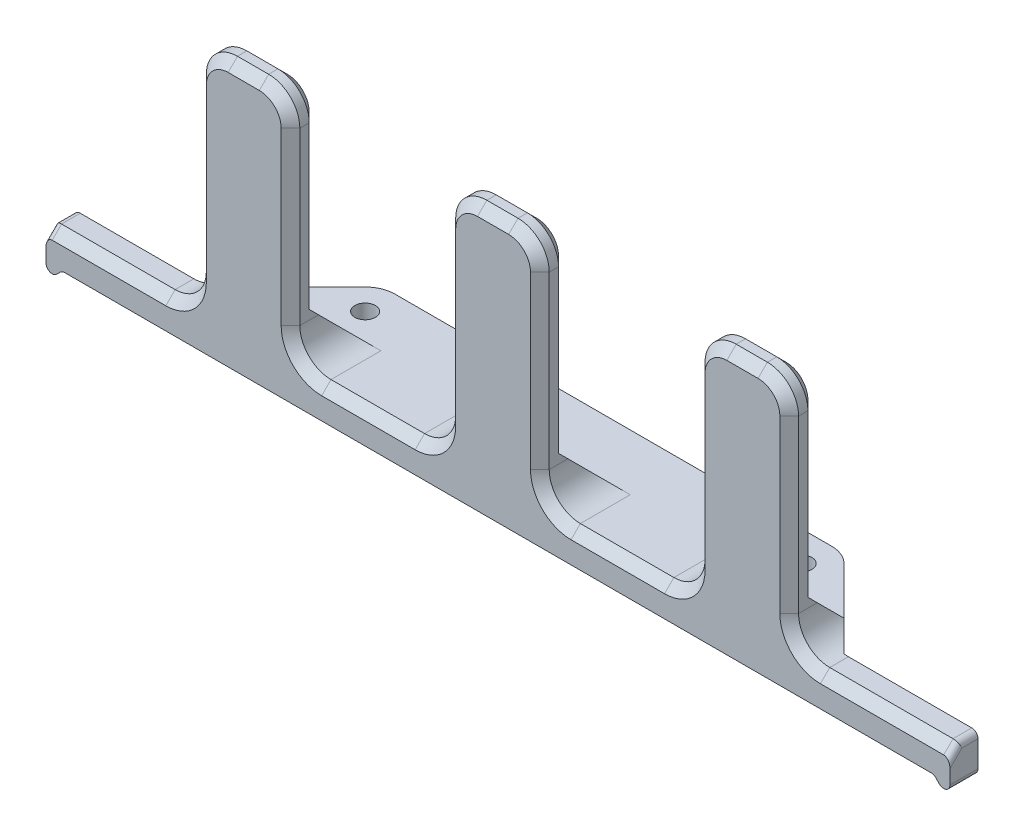
SolidWorks part; units mm, degrees
ref_plane "Front Plane" through (0, 0, 0) normal (0, 0, 1) x (1, 0, 0)
ref_plane "Top Plane" through (0, 0, 0) normal (0, 1, 0) x (1, 0, 0)
ref_plane "Right Plane" through (0, 0, 0) normal (1, 0, 0) x (0, 0, -1)
sketch "Sketch1" plane through (0, 0, 0) normal (0, 0, 1) x (1, 0, 0)
  line L0 (119.2183, -13.3858) -> (104.2183, -13.3858)
  line L1 (145, -58.3858) -> (0, -58.3858)
  line L2 (145, -58.3858) -> (145, -50.8)
  line L3 (145, -50.8) -> (0, -50.8)
  line L4 (0, -58.3858) -> (0, -50.8)
  line L5 (79.2183, -13.3858) -> (64.2183, -13.3858)
  line L6 (79.2183, -13.3858) -> (79.2183, -58.3858)
  line L8 (145, -50.8) -> (123.7883, -50.8)
  line L9 (123.7883, -50.8) -> (123.7883, -53.8)
  line L10 (123.7883, -53.8) -> (21.2117, -53.8)
  line L11 (21.2117, -53.8) -> (21.2117, -50.8)
  line L12 (21.2117, -50.8) -> (0, -50.8)
  line L13 (0, -50.8) -> (0, -58.3858)
  line L14 (2.5858, -55.8) -> (142.4142, -55.8)
  line L15 (0, -50.8) -> (0, -58.3858)
  line L16 (145, -50.8) -> (123.7883, -50.8)
  line L17 (123.7883, -50.8) -> (123.7883, -53.8)
  line L18 (123.7883, -53.8) -> (21.2117, -53.8)
  line L19 (21.2117, -53.8) -> (21.2117, -50.8)
  line L20 (21.2117, -50.8) -> (0, -50.8)
  line L24 (64.2183, -13.3858) -> (64.2183, -58.3858)
  line L25 (119.2183, -13.3858) -> (119.2183, -58.3858)
  line L26 (104.2183, -13.3858) -> (104.2183, -58.3858)
  line L27 (39.2183, -13.3858) -> (24.2183, -13.3858)
  line L28 (39.2183, -13.3858) -> (39.2183, -58.3858)
  line L29 (24.2183, -13.3858) -> (24.2183, -58.3858)
  line L46 (145, -58.3858) -> (145, -50.8)
  line L47 (145, -58.3858) -> (145, -50.8)
  line L100 (2.5858, -55.8) -> (142.4142, -55.8)
  line L101 (142.4142, -55.8) -> (145, -58.3858)
  line L102 (142.4142, -55.8) -> (145, -58.3858)
  line L103 (0, -58.3858) -> (2.5858, -55.8)
  line L104 (0, -58.3858) -> (2.5858, -55.8)
  point P6 (71.7183, -38.3858)
  dimension "D2" = 20
  dimension "D3" = 15
  dimension "D4" = 45
  dimension "D1" = 0
  dimension "D5" = 2
  dimension "D6" = 2
extrude "Boss-Extrude1" add sketch "Sketch1" along normal blind 4.5 contours L18 L25 L1 L2 L3 L17 | L3 L25 L18 L17 | L18 L26 L25 | L3 L26 L18 L25 | L0 L26 L3 L25 | L26 L18 L6 L1 | L26 L3 L6 L18 | L18 L24 L1 L6 | L3 L24 L18 L6 | L5 L24 L3 L6 | L27 L29 L3 L28 | L3 L29 L18 L28 | L18 L29 L1 L28 | L4 L29 L18 L19 L3 | L29 L3 L19 L18 | L3 L28 L18 L24 | L18 L28 L24 region at (111.7183, -32.0929, 0) region at (111.7183, -52.3, 0) region at (121.5033, -52.3, 0) region at (91.7183, -52.3, 0) region at (133.675, -53.5105, 0) region at (111.7183, -54.8, 0) region at (71.7183, -52.3, 0) region at (71.7183, -32.0929, 0) region at (91.7183, -54.8, 0) region at (51.7183, -52.3, 0) region at (71.7183, -54.8, 0) region at (31.7183, -52.3, 0) region at (31.7183, -32.0929, 0) region at (51.7183, -54.8, 0) region at (22.715, -52.3, 0) region at (31.7183, -54.8, 0) region at (10.9545, -53.4755, 0)
sketch "Sketch2" plane through (0, -53.8, 0) normal (0, 1, 0) x (1, 0, 0)
  line L0 (123.5054, 0) -> (110.9064, 12.599)
  line L1 (107.5123, 14.0049) -> (37.4877, 14.0049)
  line L2 (34.0936, 12.599) -> (21.4946, 0)
  line L4 (107.5123, 14.2049) -> (37.4877, 14.2049)
  line L5 (33.9522, 12.7405) -> (21.2117, 0)
  line L6 (21.2117, 0) -> (123.7883, 0)
  line L7 (123.7883, 0) -> (111.0478, 12.7405)
  line L10 (21.4946, 0) -> (123.5054, 0)
  circle A0 centre (37.4877, 9.2049) radius 1.65 construction
  circle A1 centre (107.5123, 9.2049) radius 1.65 construction
  arc A2 (37.4877, 14.2049) -> (33.9522, 12.7405) centre (37.4877, 9.2049) ccw
  arc A3 (111.0478, 12.7405) -> (107.5123, 14.2049) centre (107.5123, 9.2049) ccw
  circle A6 centre (37.4877, 9.2049) radius 1.65
  circle A7 centre (107.5123, 9.2049) radius 1.65
  arc A8 (110.9064, 12.599) -> (107.5123, 14.0049) centre (107.5123, 9.2049) ccw
  arc A9 (37.4877, 14.0049) -> (34.0936, 12.599) centre (37.4877, 9.2049) ccw
  dimension "D1" = 0
extrude "Boss-Extrude2" add sketch "Sketch2" along normal up to surface (3 mm away)
chamfer "Chamfer1" distance 5 angle 45 3 edges at (31.7183, -50.8, 0) (71.7183, -50.8, 0) (111.7183, -50.8, 0)
fillet "Fillet1" radius 5 6 edges at (39.2183, -50.8, -0.25) (24.2183, -50.8, 0.8881) (64.2183, -50.8, -0.25) (79.2183, -50.8, -0.25) (119.2183, -50.8, 0.1064) (104.2183, -50.8, -0.25)
fillet "Fillet2" radius 5 6 edges at (119.2183, -13.3858, 2.25) (104.2183, -13.3858, 2.25) (79.2183, -13.3858, 2.25) (64.2183, -13.3858, 2.25) (39.2183, -13.3858, 2.25) (24.2183, -13.3858, 2.25)
chamfer "Chamfer2" distance 1.5 angle 45 15 edges at (119.2183, -32.0929, 0) (117.7538, -14.8503, 0) (111.7183, -13.3858, 0) (105.6827, -14.8503, 0) (104.2183, -32.0929, 0) (79.2183, -32.0929, 0) (77.7538, -14.8503, 0) (71.7183, -13.3858, 0) (65.6827, -14.8503, 0) (64.2183, -32.0929, 0) (39.2183, -32.0929, 0) (37.7538, -14.8503, 0) (31.7183, -13.3858, 0) (25.6827, -14.8503, 0) (24.2183, -32.0929, 0)
chamfer "Chamfer3" distance 1.5 angle 45 8 edges at (120.6827, -49.3355, 4.5) (119.2183, -32.0929, 4.5) (117.7538, -14.8503, 4.5) (111.7183, -13.3858, 4.5) (105.6827, -14.8503, 4.5) (104.2183, -32.0929, 4.5) (102.7538, -49.3355, 4.5) (134.6091, -50.8, 4.5)
fillet "Fillet3" radius 1 8 edges at (0, -51.55, 3.75) (0, -50.8, 1.5) (145, -51.55, 3.75) (145, -50.8, 1.5) (142.4142, -55.8, 2.25) (2.5858, -55.8, 2.25) (0, -58.3858, 2.25) (145, -58.3858, 2.25)
